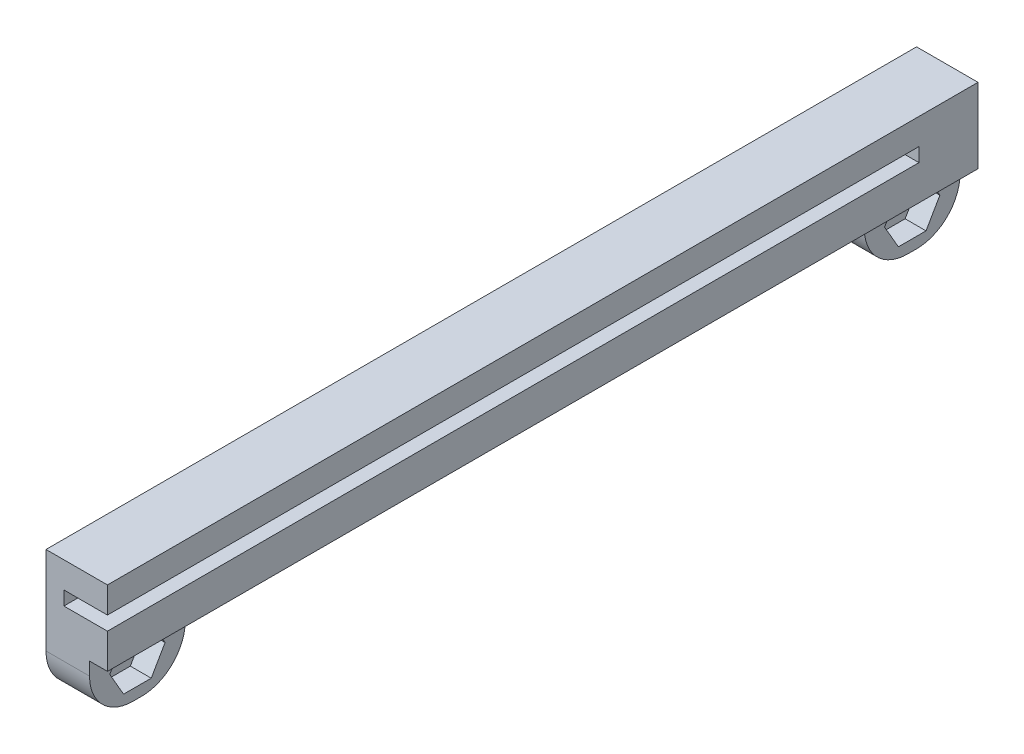
SolidWorks part; units mm, degrees
ref_plane "Front Plane" through (0, 0, 0) normal (0, 0, 1) x (1, 0, 0)
ref_plane "Top Plane" through (0, 0, 0) normal (0, 1, 0) x (1, 0, 0)
ref_plane "Right Plane" through (0, 0, 0) normal (1, 0, 0) x (0, 0, -1)
sketch "Sketch1" plane through (0, 0, 0) normal (0, 1, 0) x (1, 0, 0)
  line L1 (-3.5288, -50) -> (3.5288, -50)
  line L2 (-3.5288, -50) -> (-3.5288, 50)
  line L3 (-3.5288, 50) -> (3.5288, 50)
  line L4 (3.5288, -50) -> (3.5288, 50)
  line L5 (-3.5288, -50) -> (3.5288, 50) construction
  line L6 (-3.5288, 50) -> (3.5288, -50) construction
  point P0 (0, 0)
  dimension "D1" = 100
  dimension "D2" = 7.0575
extrude "Boss-Extrude2" add sketch "Sketch1" along normal blind 7.6
sketch "Sketch4" plane through (0, 7.6, 0) normal (0, 1, 0) x (1, 0, 0)
  line L0 (3.5288, -50) -> (3.5288, 50) construction
  line L1 (3.5288, 43.218) -> (-1.4713, 43.218)
  line L2 (3.5288, 43.218) -> (3.5288, -50)
  line L3 (3.5288, -50) -> (-1.4713, -50)
  line L4 (-1.4713, 43.218) -> (-1.4713, -50)
  line L6 (3.5288, 50) -> (-3.5288, 50) construction
  line L7 (-3.5288, 50) -> (-3.5288, -50) construction
  dimension "D1" = 6.782
  dimension "D2" = 2.0575
extrude "Cut-Extrude1" cut sketch "Sketch4" against normal blind 4.6
sketch "Sketch6" plane through (0, 7.6, 0) normal (0, 1, 0) x (1, 0, 0)
  line L1 (3.5288, 43.218) -> (-1.4713, 43.218)
  line L2 (3.5288, 43.218) -> (3.5288, -50)
  line L3 (3.5288, -50) -> (-1.4713, -50)
  line L4 (-1.4713, 43.218) -> (-1.4713, -50)
extrude "Boss-Extrude3" add sketch "Sketch6" against normal blind 3
sketch "Sketch8" plane through (0, 0, 0) normal (0, -1, 0) x (1, 0, 0)
  line L1 (-3.5288, 50) -> (3.5288, 50)
  line L2 (-3.5288, 50) -> (-3.5288, -50)
  line L3 (-3.5288, -50) -> (3.5288, -50)
  line L4 (3.5288, 50) -> (3.5288, -50)
extrude "Boss-Extrude4" add sketch "Sketch8" along normal blind 1
sketch "Sketch9" plane through (0, -1, 0) normal (0, -1, 0) x (1, 0, 0)
  line L1 (-3.5288, 50) -> (1.4712, 50)
  line L2 (-3.5288, 50) -> (-3.5288, 39)
  line L3 (-3.5288, 39) -> (1.4712, 39)
  line L4 (1.4712, 50) -> (1.4712, 39)
  line L5 (-3.5288, -50) -> (1.4712, -50)
  line L6 (-3.5288, -50) -> (-3.5288, -39)
  line L7 (-3.5288, -39) -> (1.4712, -39)
  line L8 (1.4712, -50) -> (1.4712, -39)
  point P10 (1.4712, -44.5)
  dimension "D1" = 11
  dimension "D2" = 11
  dimension "D3" = 5
  dimension "D4" = 5
extrude "Boss-Extrude5" add sketch "Sketch9" along normal blind 6.5 contours L2 L1 L4 L3 | L6 L5 L8 L7
sketch "Sketch10" plane through (1.4713, 0, 0) normal (1, 0, 0) x (0, 0, -1)
  line L0 (-50, -7.5) -> (-50, -1) construction
  line L1 (-46.0877, -0.75) -> (-47.6754, -3.5)
  line L2 (-47.6754, -3.5) -> (-46.0877, -6.25)
  line L3 (-46.0877, -6.25) -> (-42.9123, -6.25)
  line L4 (-42.9123, -6.25) -> (-41.3246, -3.5)
  line L5 (-41.3246, -3.5) -> (-42.9123, -0.75)
  line L6 (-42.9123, -0.75) -> (-46.0877, -0.75)
  line L7 (-50, -7.5) -> (-39, -7.5) construction
  line L8 (39, -7.5) -> (39, -1) construction
  line L9 (47.6754, -3.5) -> (46.0877, -0.75)
  line L10 (46.0877, -0.75) -> (42.9123, -0.75)
  line L11 (42.9123, -0.75) -> (41.3246, -3.5)
  line L12 (41.3246, -3.5) -> (42.9123, -6.25)
  line L13 (42.9123, -6.25) -> (46.0877, -6.25)
  line L14 (46.0877, -6.25) -> (47.6754, -3.5)
  line L15 (50, -7.5) -> (39, -7.5) construction
  circle A0 centre (-44.5, -3.5) radius 2.75 construction
  circle A1 centre (44.5, -3.5) radius 2.75 construction
  dimension "D1" = 5.5
  dimension "D2" = 5.5
  dimension "D3" = 1.25
  dimension "D4" = 5.5
  dimension "D5" = 1.25
  dimension "D6" = 5.5
extrude "Cut-Extrude2" cut sketch "Sketch10" against normal blind 2.4
sketch "Sketch11" plane through (-0.9287, 0, 0) normal (1, 0, 0) x (0, 0, -1)
  line L2 (-50, -7.5) -> (-39, -7.5) construction
  line L3 (-50, -7.5) -> (-50, -1) construction
  line L4 (39, -7.5) -> (39, -1) construction
  line L5 (50, -7.5) -> (39, -7.5) construction
  circle A0 centre (-44.5, -3.5) radius 1.5
  circle A1 centre (44.5, -3.5) radius 1.5
  dimension "D3" = 3
  dimension "D4" = 3
  dimension "D1" = 4
  dimension "D2" = 5.5
  dimension "D5" = 5.5
  dimension "D6" = 4
extrude "Cut-Extrude3" cut sketch "Sketch11" against normal through all contours A0 | A1
fillet "Fillet2" radius 5 4 edges at (-1.0288, -7.5, -50) (-1.0288, -7.5, -39) (-1.0288, -7.5, 39) (-1.0288, -7.5, 50)
